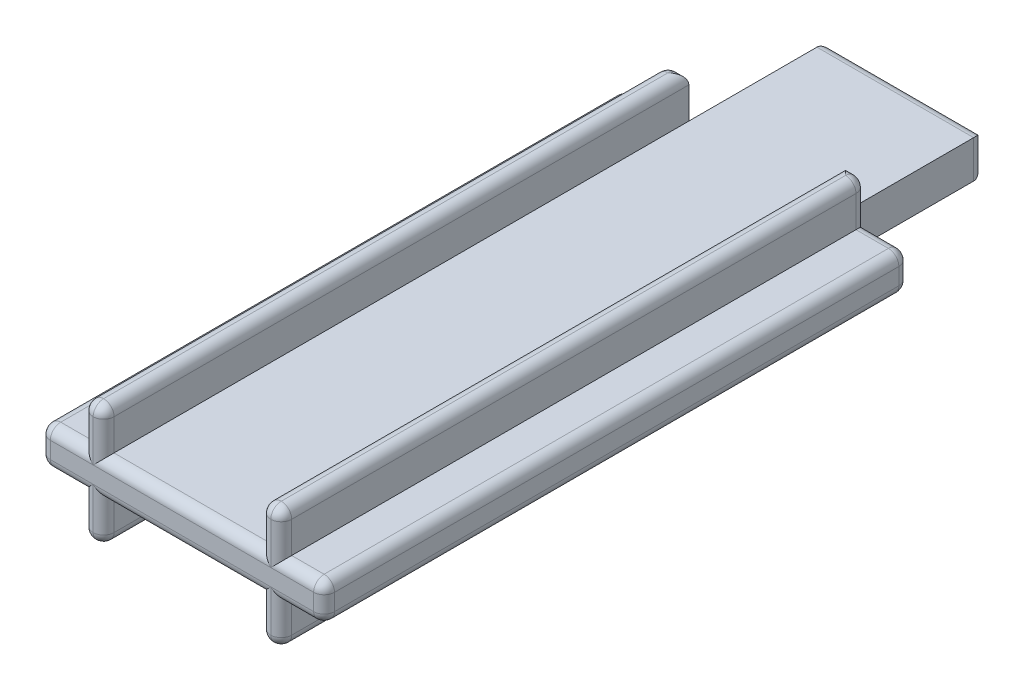
SolidWorks part; units mm, degrees
ref_plane "Ebene vorne" through (0, 0, 0) normal (0, 0, 1) x (1, 0, 0)
ref_plane "Ebene oben" through (0, 0, 0) normal (0, 1, 0) x (1, 0, 0)
ref_plane "Ebene rechts" through (0, 0, 0) normal (1, 0, 0) x (0, 0, -1)
sketch "Skizze1" plane through (0, 0, 0) normal (0, 0, 1) x (1, 0, 0)
  line L0 (-4.75, 0.9) -> (-6.8, 0.9)
  line L1 (6.8, -0.9) -> (4.75, -0.9)
  line L2 (6.8, -0.9) -> (6.8, 0.9)
  line L3 (6.8, 0.9) -> (4.75, 0.9)
  line L4 (-6.8, -0.9) -> (-6.8, 0.9)
  line L5 (6.8, -0.9) -> (-6.8, 0.9) construction
  line L6 (6.8, 0.9) -> (-6.8, -0.9) construction
  line L7 (-4.75, -2.9) -> (-3.75, -2.9)
  line L8 (-4.75, -2.9) -> (-4.75, -0.9)
  line L9 (-4.75, 2.9) -> (-3.75, 2.9)
  line L10 (-3.75, -2.9) -> (-3.75, -0.9)
  line L11 (-4.75, -2.9) -> (-3.75, 2.9) construction
  line L12 (-4.75, 2.9) -> (-3.75, -2.9) construction
  line L13 (4.75, -2.9) -> (3.75, -2.9)
  line L14 (4.75, -2.9) -> (4.75, -0.9)
  line L15 (4.75, 2.9) -> (3.75, 2.9)
  line L16 (3.75, -2.9) -> (3.75, -0.9)
  line L17 (4.75, -2.9) -> (3.75, 2.9) construction
  line L18 (4.75, 2.9) -> (3.75, -2.9) construction
  line L19 (-4.75, -0.9) -> (-6.8, -0.9)
  line L20 (-4.75, 0.9) -> (-4.75, 2.9)
  line L21 (-3.75, 0.9) -> (-3.75, 2.9)
  line L22 (3.75, -0.9) -> (-3.75, -0.9)
  line L23 (3.75, 0.9) -> (3.75, 2.9)
  line L24 (4.75, 0.9) -> (4.75, 2.9)
  line L25 (3.75, 0.9) -> (-3.75, 0.9)
  point P0 (0, 0)
  point P5 (-4.25, 0)
  point P11 (4.25, 0)
  point P16 (2.3798, 0)
  point P17 (-3.9686, 0)
  point P18 (4.683, 0.0484)
  point P19 (0, 0)
  point P20 (-4.2009, 0)
  dimension "D1" = 1.8
  dimension "D2" = 5.8
  dimension "D3" = 13.6
  dimension "D4" = 9.5
  dimension "D5" = 1
  dimension "D6" = 4.75
extrude "Aufsatz-Linear austragen1" add sketch "Skizze1" along normal blind 28
sketch "Skizze2" plane through (0, 0, 0) normal (0, 0, -1) x (-1, 0, 0)
  line L1 (3.75, -0.9) -> (-3.75, -0.9)
  line L2 (3.75, -0.9) -> (3.75, 0.9)
  line L3 (3.75, 0.9) -> (-3.75, 0.9)
  line L4 (-3.75, -0.9) -> (-3.75, 0.9)
  line L5 (3.75, -0.9) -> (-3.75, 0.9) construction
  line L6 (3.75, 0.9) -> (-3.75, -0.9) construction
  point P0 (0, 0)
extrude "Aufsatz-Linear austragen2" add sketch "Skizze2" along normal blind 6.63
fillet "Verrundung1" radius 0.5 46 edges at (-5.775, 0.9, 28) (-4.75, 1.9, 28) (-3.75, 1.9, 28) (0, 0.9, 28) (3.75, 1.9, 28) (4.75, 1.9, 28) (5.775, 0.9, 28) (5.775, -0.9, 28) (4.75, -1.9, 28) (3.75, -1.9, 28) (0, -0.9, 28) (-3.75, -1.9, 28) (-4.75, -1.9, 28) (-5.775, -0.9, 28) (0, 0.9, -6.63) (-3.75, 0, -6.63) (0, -0.9, -6.63) (3.75, 0, -6.63) (-6.8, 0.9, 14) (-6.8, 0, 28) (-6.8, -0.9, 14) (-6.8, 0, 0) (6.8, -0.9, 14) (6.8, 0, 28) (6.8, 0.9, 14) (6.8, 0, 0) (-4.75, -2.9, 14) (-3.75, -2.9, 14) (-4.25, -2.9, 0) (3.75, -2.9, 14) (4.75, -2.9, 14) (4.25, -2.9, 0) (-3.75, 2.9, 14) (-4.75, 2.9, 14) (-4.25, 2.9, 0) (4.75, 2.9, 14) (3.75, 2.9, 14) (4.25, 2.9, 0) (4.75, 1.9, 0) (5.775, 0.9, 0) (5.775, -0.9, 0) (4.75, -1.9, 0) (-4.75, 1.9, 0) (-4.75, -1.9, 0) (-5.775, 0.9, 0) (-5.775, -0.9, 0)
